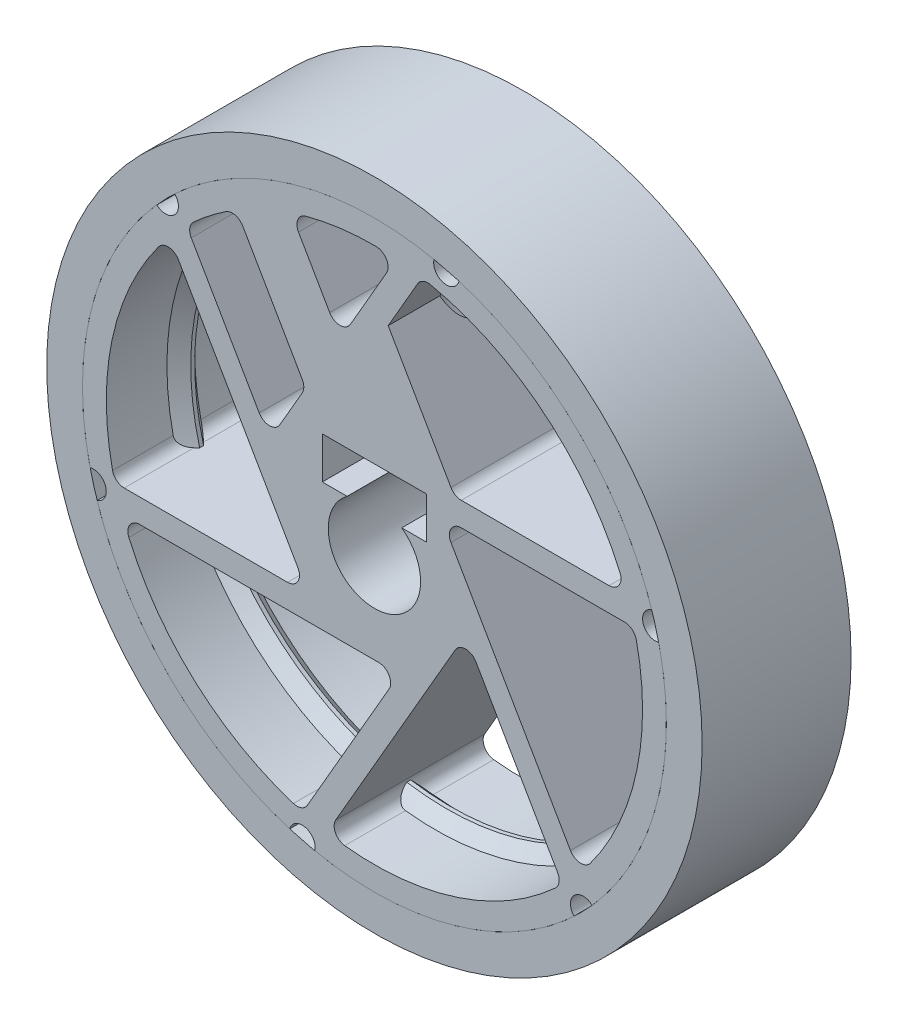
SolidWorks part; units mm, degrees
other "tire-mock"
other "hub"
ref_plane "Front Plane" through (0, 0, 0) normal (0, 0, 1) x (1, 0, 0)
ref_plane "Top Plane" through (0, 0, 0) normal (0, 1, 0) x (1, 0, 0)
ref_plane "Right Plane" through (0, 0, 0) normal (1, 0, 0) x (0, 0, -1)
sketch "Sketch1" plane through (0, 0, 0) normal (0, 0, 1) x (1, 0, 0)
  line L0 (1.833, 2.5) -> (3.5, 2.5)
  line L1 (3.5, 2.5) -> (3.5, 5.3)
  line L2 (3.5, 5.3) -> (-3.5, 5.3)
  line L3 (-3.5, 5.3) -> (-3.5, 2.5)
  line L4 (-3.5, 2.5) -> (-1.833, 2.5)
  line L5 (-1.6583, 2.5) -> (1.6583, 2.5) construction
  line L6 (-7.0437, 0) -> (-13.7502, 11.616)
  line L7 (3.5218, -6.1) -> (7.0437, 0) construction
  line L8 (7.0437, 0) -> (3.5218, 6.1) construction
  line L9 (3.5218, 6.1) -> (-3.5218, 6.1) construction
  line L10 (-3.5218, 6.1) -> (-7.0437, 0) construction
  line L11 (-7.0437, 0) -> (-3.5218, -6.1) construction
  line L12 (-3.5218, -6.1) -> (3.5218, -6.1) construction
  line L13 (-3.5218, -6.1) -> (-16.9349, -6.1)
  line L14 (3.5218, -6.1) -> (-3.1847, -17.716)
  line L15 (7.0437, 0) -> (13.7502, -11.616)
  line L16 (-6.1199, 1.6) -> (-12.6113, 12.8435) construction
  line L17 (6.1199, -1.6) -> (12.6113, -12.8435)
  line L18 (1.6743, -6.1) -> (-4.8171, -17.3435)
  line L19 (-4.4456, -4.5) -> (-17.4284, -4.5)
  line L20 (3.5218, 6.1) -> (16.9349, 6.1) construction
  line L21 (4.4456, 4.5) -> (17.4284, 4.5)
  line L22 (-12.6113, 12.8435) -> (-7.0437, 3.2)
  line L23 (-7.0437, 3.2) -> (-3.4613, 9.4048)
  line L24 (-3.4613, 9.4048) -> (3.4613, 9.4048) construction
  line L25 (3.4613, 9.4048) -> (5.3694, 6.1)
  line L26 (5.3694, 6.1) -> (16.9349, 6.1)
  line L29 (-7.0437, 0) -> (-4.4456, -4.5)
  line L30 (-3.5218, -6.1) -> (1.6743, -6.1)
  line L31 (3.5218, -6.1) -> (6.1199, -1.6)
  line L32 (7.0437, 0) -> (4.4456, 4.5)
  line L33 (-3.4613, 9.4048) -> (1.4666, 17.9402)
  line L34 (3.1847, 17.716) -> (-1.6138, 9.4048)
  line L35 (3.4613, 9.4048) -> (-1.6138, 9.4048)
  line L36 (11.1521, 6.1) -> (11.1521, 4.5) construction
  line L37 (-0.9974, 13.6725) -> (0.3883, 12.8725) construction
  circle A0 centre (0, 0) radius 3 construction
  circle A1 centre (0, 0) radius 3.1 construction
  arc A2 (-1.833, 2.5) -> (1.833, 2.5) centre (0, 0) ccw
  circle A3 centre (0, 0) radius 6.1 construction
  circle A4 centre (0, 0) radius 22 construction
  circle A6 centre (0, 0) radius 19.6
  circle A7 centre (0, 0) radius 18 construction
  arc A8 (1.4666, 17.9402) -> (-12.6113, 12.8435) centre (0, 0) ccw
  arc A9 (-13.7502, 11.616) -> (-17.4284, -4.5) centre (0, 0) ccw
  arc A10 (-4.8171, -17.3435) -> (-16.9349, -6.1) centre (0, 0) cw
  arc A11 (12.6113, -12.8435) -> (-3.1847, -17.716) centre (0, 0) cw
  arc A12 (17.4284, 4.5) -> (13.7502, -11.616) centre (0, 0) cw
  arc A13 (16.9349, 6.1) -> (3.1847, 17.716) centre (0, 0) ccw
  point P13 (0, -3)
  point P43 (0, 9.4048)
  point P55 (-19.6, 0)
  point P56 (19.6, 0)
  point P58 (0, -19.6)
  point P59 (0, 19.6)
  point P61 (-18, 0)
  point P65 (0, 0)
  point P66 (0, 0)
  point P67 (0, 0)
  dimension "D1" = 6
  dimension "D7" = 44
  dimension "D3" = 7
  dimension "D4" = 2.8
  dimension "D5" = 5.5
  dimension "D6" = 0.8
  dimension "D10" = 1.6
  dimension "D11" = 4.1048
  dimension "D12" = 1.6
  dimension "D2" = 0.1
  dimension "D8" = 2.4
  dimension "D9" = 1.6
extrude "Boss-Extrude1" add sketch "Sketch1" along normal blind 10
ref_axis "Axis1" through (0, 0, 10) along (0, 0, -1)
sketch "Sketch9" plane through (0, 0, 0) normal (0, 0, -1) x (-1, 0, 0)
  line L0 (-3.4613, 9.4048) -> (-0.9238, 13.8)
  line L1 (-3.4613, 9.4048) -> (-5.3694, 6.1) construction
  line L2 (-3.1847, 17.716) -> (1.6138, 9.4048) construction
  line L3 (-0.9238, 13.8) -> (1.6138, 9.4048)
  line L4 (1.6138, 9.4048) -> (-3.4613, 9.4048)
extrude "Boss-Extrude3" add sketch "Sketch9" against normal up to surface (10 mm away) up to face at (19.6, 0, 10)
sketch "Sketch10" plane through (0, 0, 0) normal (0, 0, -1) x (-1, 0, 0)
  line L0 (2.3094, 11.4) -> (6.4195, 18.5189)
  line L1 (3.4613, 9.4048) -> (-1.4666, 17.9402) construction
  line L2 (6.4195, 18.5189) -> (10.0587, 16.8221)
  line L3 (10.0587, 16.8221) -> (4.6188, 7.4)
  line L4 (4.6188, 7.4) -> (2.3094, 11.4)
  line L5 (-3.4613, 9.4048) -> (-5.3694, 6.1) construction
  circle A0 centre (0, 0) radius 19.6 construction
  point P4 (0, 0)
  point P9 (0, 0)
  dimension "D1" = 4
  dimension "D2" = 4
extrude "Boss-Extrude6" add sketch "Sketch10" against normal up to surface (10 mm away) up to face at (6.9922, 11.3896, 10)
fillet "Fillet1" radius 0.8 8 edges at (4.4456, 4.5, 5) (6.1199, -1.6, 5) (1.6743, -6.1, 5) (-4.4456, -4.5, 5) (-7.0437, 3.2, 5) (5.3694, 6.1, 5) (-4.6188, 7.4, 5) (-2.3094, 11.4, 5)
fillet "Fillet2" radius 0.8 8 edges at (13.7502, -11.616, 5) (16.9349, 6.1, 5) (-13.7502, 11.616, 5) (-16.9349, -6.1, 5) (-3.1847, -17.716, 5) (1.4666, 17.9402, 5) (-9.2586, 15.4363, 5) (-5.6035, 17.1056, 5)
fillet "Fillet3" radius 0.8 6 edges at (-17.4284, -4.5, 5) (-12.6113, 12.8435, 5) (17.4284, 4.5, 5) (12.6113, -12.8435, 5) (-4.8171, -17.3435, 5) (3.1847, 17.716, 5)
sketch "Sketch8" [suppressed] plane through (0, 0, 10) normal (0, 0, 1) x (1, 0, 0)
  line L1 (-3.4613, 18.0715) -> (3.4613, 18.0715)
  line L2 (-3.4613, 18.0715) -> (-3.4613, 9.4048)
  line L3 (-3.4613, 9.4048) -> (3.4613, 9.4048)
  line L4 (3.4613, 18.0715) -> (3.4613, 9.4048)
  line L5 (0, 9.4048) -> (0, 18.0715) construction
  line L6 (-3.4613, 13.7382) -> (3.4613, 13.7382) construction
  circle A0 centre (0, 0) radius 18.4 construction
  point P0 (0, 13.7382)
  point P4 (0, 0)
  point P5 (0, 0)
  point P8 (0, 0)
extrude "Boss-Extrude2" [suppressed] add sketch "Sketch8" against normal up to surface (10 mm away) up to face at (-8.386, 9.8494, 0)
sketch "Sketch2" plane through (0, 5.3, 0) normal (0, -1, 0) x (1, 0, 0)
  line L0 (0, 10) -> (0, 0) construction
  line L1 (3.5, 10) -> (-3.5, 10) construction
  line L2 (3.5, 0) -> (-3.5, 0) construction
  circle A0 centre (0, 5) radius 1.8
  dimension "D1" = 3.6
extrude "Cut-Extrude1" cut sketch "Sketch2" against normal up to surface (12.6098 mm away) up to face at (10.7501, 13.1804, 5)
sketch "Sketch5" plane through (0, 0, 0) normal (0, 1, 0) x (1, 0, 0)
  line L0 (-19.6, -3.6) -> (-19.6, -6.4)
  line L3 (-19.6, -3.6) -> (-18.8, -4.4)
  line L4 (-18.8, -4.4) -> (-18.8, -5.6)
  line L5 (-18.8, -5.6) -> (-19.6, -6.4)
  point P3 (-19.6, -5)
  dimension "D1" = 0.8
  dimension "D2" = 45
  dimension "D3" = 1.2
sketch "Sketch7" plane through (0, 0, 0) normal (0, 1, 0) x (1, 0, 0)
  line L0 (-19.6, -2.4686) -> (-19.6, -7.5314)
  line L1 (-19.6, -7.5314) -> (-17.2, -5.1314)
  line L2 (-17.2, -5.1314) -> (-17.2, -4.8686)
  line L3 (-17.2, -4.8686) -> (-19.6, -2.4686)
  line L4 (-18.8, -5.6) -> (-19.6, -6.4) construction
  line L5 (-19.6, -3.6) -> (-19.6, -6.4) construction
  line L6 (-18.8, -4.4) -> (-18.8, -5.6) construction
  point P6 (-19.6, -5)
  dimension "D1" = 1.6
  dimension "D2" = 0.8
revolve "Revolve1" add sketch "Sketch7" angle 360 about axis through (0, 0, 10) along (0, 0, -1)
sketch "Sketch6" plane through (0, 5.3, 0) normal (0, -1, 0) x (1, 0, 0)
  circle A0 centre (0, 5) radius 1.4
  dimension "D1" = 2.8
extrude "Cut-Extrude3" cut sketch "Sketch6" against normal through all
sketch "Sketch3" plane through (0, 0, 10) normal (0, 0, 1) x (1, 0, 0)
  line L0 (2.5981, -6.1) -> (-4.845, -18.9917) construction
  line L1 (-3.5218, -6.1) -> (3.5218, -6.1) construction
  line L2 (1.6743, -6.1) -> (-4.8171, -17.3435) construction
  line L3 (1.6743, -6.1) -> (3.5218, -6.1) construction
  circle A0 centre (-4.845, -18.9917) radius 0.8678
  circle A1 centre (0, 0) radius 19.6 construction
  circle A2 centre (0, 0) radius 18 construction
  circle A3 centre (-18.8698, -5.3) radius 0.8678
  circle A4 centre (-14.0248, 13.6917) radius 0.8678
  circle A5 centre (4.845, 18.9917) radius 0.8678
  circle A6 centre (18.8698, 5.3) radius 0.8678
  circle A7 centre (14.0248, -13.6917) radius 0.8678
  point P14 (2.5981, -6.1)
  point P15 (-4.4111, -18.2402)
  point P16 (-4.0111, -17.5474)
  point P32 (0, 0)
  dimension "D1" = 0.8
  dimension "D2" = 6
extrude "Cut-Extrude2" cut sketch "Sketch3" against normal through all
revolve "Cut-Revolve2" cut sketch "Sketch5" angle 360 about axis through (0, 0, 10) along (0, 0, -1)
sketch "Sketch11" plane through (0, 0, 10) normal (0, 0, 1) x (1, 0, 0)
  circle A0 centre (0, 0) radius 22 construction
  circle A1 centre (0, 0) radius 22
  circle A2 centre (0, 0) radius 19.6 construction
  circle A3 centre (0, 0) radius 19.6
extrude "Boss-Extrude7" add sketch "Sketch11" against normal up to surface (10 mm away) separate body up to face at (-8.386, 9.8494, 0)
